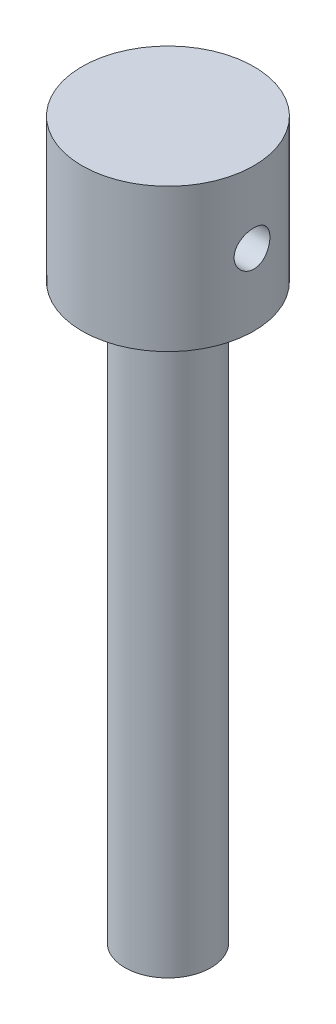
SolidWorks part; units mm, degrees
ref_plane "Front Plane" through (0, 0, 0) normal (0, 0, 1) x (1, 0, 0)
ref_plane "Top Plane" through (0, 0, 0) normal (0, 1, 0) x (1, 0, 0)
ref_plane "Right Plane" through (0, 0, 0) normal (1, 0, 0) x (0, 0, -1)
sketch "Sketch1" plane through (0, 0, 0) normal (0, 1, 0) x (1, 0, 0)
  circle A0 centre (0, 0) radius 152.4
  circle A1 centre (0, 0) radius 304.8
  dimension "D1" = 304.8
  dimension "D2" = 609.6
extrude "Boss-Extrude1" add sketch "Sketch1" against normal blind 2540 contours A0 region at (0, 0, 0)
extrude "Boss-Extrude2" add sketch "Sketch1<3>" against normal blind 508
sketch "Sketch1<3>" plane through (0, 0, 0) normal (0, 1, 0) x (1, 0, 0) same geometry as "Sketch1"
sketch "Sketch2" plane through (0, 0, 0) normal (1, 0, 0) x (0, 0, -1)
  line L0 (304.8, 0) -> (-304.8, 0) construction
  circle A0 centre (0, -254) radius 63.5
  dimension "D2" = 127
  dimension "D1" = 254
extrude "Cut-Extrude1" cut sketch "Sketch2" against normal through all both and the other way through all
equation "\"A\"=100"
equation "\"D1@Boss-Extrude1\"=\"A\""
